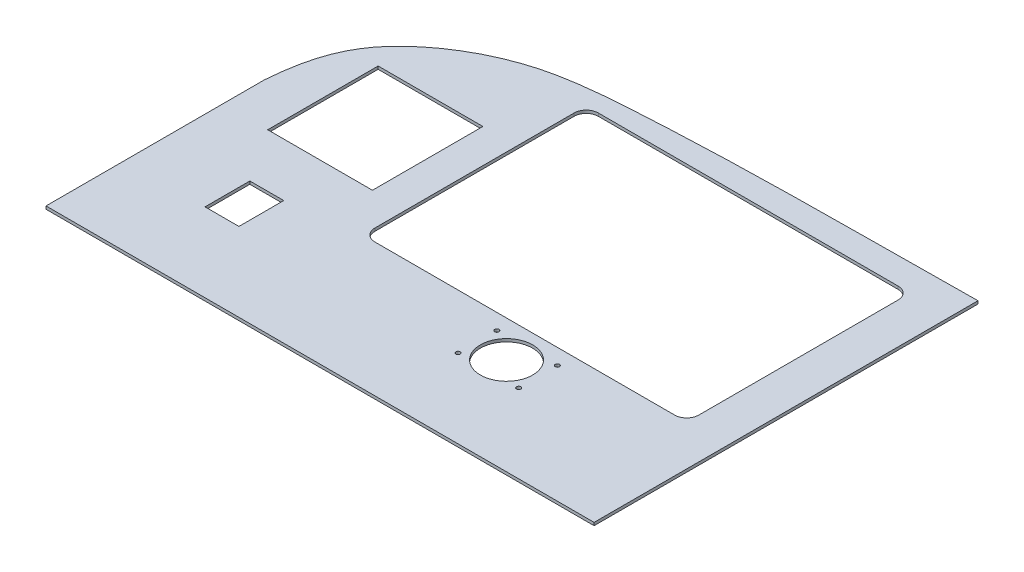
SolidWorks part; units mm, degrees
ref_plane "Alzado" through (0, 0, 0) normal (0, 0, 1) x (1, 0, 0)
ref_plane "Planta" through (0, 0, 0) normal (0, 1, 0) x (1, 0, 0)
ref_plane "Vista lateral" through (0, 0, 0) normal (1, 0, 0) x (0, 0, -1)
sketch "Croquis1" plane through (0, 0, 0) normal (0, 1, 0) x (1, 0, 0)
  line L0 (-226.279, 0) -> (226.279, 0)
  line L1 (226.279, 0) -> (226.279, 317)
  line L2 (-159.971, 65) -> (-131.971, 65)
  line L11 (-64.721, 294.5) -> (182.779, 294.5)
  line L12 (-74.721, 284.5) -> (-74.721, 120)
  line L13 (-64.721, 110) -> (182.779, 110)
  line L14 (192.779, 284.5) -> (192.779, 120)
  line L15 (-189.221, 237.2) -> (-102.721, 237.2)
  line L16 (-226.279, 0) -> (-226.279, 180)
  line L17 (-189.221, 237.2) -> (-189.221, 146)
  line L18 (-189.221, 146) -> (-102.721, 146)
  line L19 (-102.721, 237.2) -> (-102.721, 146)
  line L24 (-159.971, 65) -> (-159.971, 102)
  line L25 (-159.971, 102) -> (-131.971, 102)
  line L26 (-131.971, 65) -> (-131.971, 102)
  circle A10 centre (73.979, 80) radius 21.6
  arc A11 (182.779, 110) -> (192.779, 120) centre (182.779, 120) ccw
  arc A12 (-64.721, 110) -> (-74.721, 120) centre (-64.721, 120) cw
  arc A13 (182.779, 294.5) -> (192.779, 284.5) centre (182.779, 284.5) cw
  arc A14 (-64.721, 294.5) -> (-74.721, 284.5) centre (-64.721, 284.5) ccw
  circle A15 centre (48.979, 97) radius 1.75
  circle A16 centre (98.979, 97) radius 1.75
  circle A17 centre (98.979, 65) radius 1.75
  circle A18 centre (48.979, 65) radius 1.75
  spline S0 degree 3 poles (-226.279, 180) (-223.6672, 215.4766) (-213.4119, 241.7289) (-180.591, 273.8979) (-156.3503, 289.27) (-113.0678, 305.0472) (-89.4215, 307.6374) (-74, 309.1757) knots 0 0 0 0 0.358065 0.430061 0.687747 0.747962 1 1 1 1
  spline S1 degree 3 poles (226.279, 317) (126.0586, 315.5305) (25.9571, 316.9126) (-74, 309.1757) knots 0 0 0 0 1 1 1 1
  point P4 (0, 0)
  point P15 (-74.721, 110)
  point P20 (192.779, 294.5)
  point P24 (-74.721, 294.5)
  point P32 (-145.971, 146)
  point P35 (-145.971, 102)
  dimension "D7" = 65
  dimension "D8" = 28
  dimension "D12" = 317
  dimension "D3" = 43.2
  dimension "D4" = 30
  dimension "D5" = 10
  dimension "D6" = 152.3
  dimension "D9" = 3.5
  dimension "D10" = 25
  dimension "D11" = 17
  dimension "D2" = 180
  dimension "D14" = 37
  dimension "D16" = 267.5
  dimension "D17" = 184.5
  dimension "D18" = 86.5
  dimension "D19" = 91.2
  dimension "D20" = 33.5
  dimension "D21" = 110
  dimension "D22" = 28
  dimension "D23" = 146
  dimension "D24" = 2
  dimension "D25" = 2
extrude "Saliente-Extruir1" add sketch "Croquis1" along normal blind 2.4
